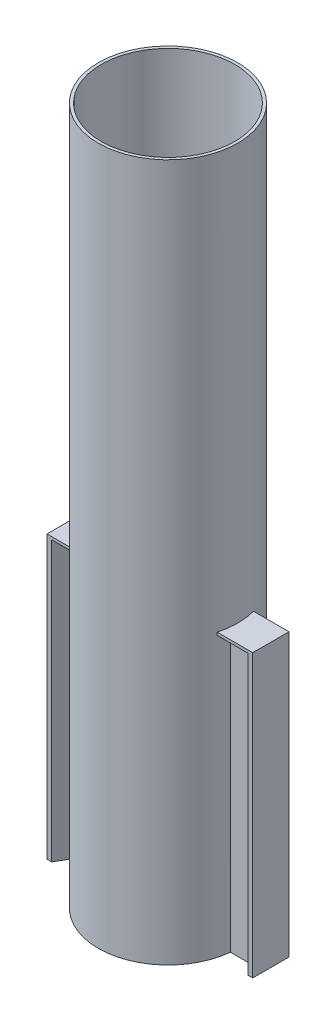
SolidWorks part; units mm, degrees
ref_plane "Спереди" through (0, 0, 0) normal (0, 0, 1) x (1, 0, 0)
ref_plane "Сверху" through (0, 0, 0) normal (0, 1, 0) x (1, 0, 0)
ref_plane "Справа" through (0, 0, 0) normal (1, 0, 0) x (0, 0, -1)
sketch "Эскиз1" plane through (0, 0, 0) normal (0, 1, 0) x (1, 0, 0)
  circle A0 centre (0, 0) radius 25
  circle A1 centre (0, 0) radius 22.5
  dimension "D1" = 50
  dimension "D2" = 45
extrude "Бобышка-Вытянуть1" add sketch "Эскиз1" along normal blind 160
sketch "Эскиз2" plane through (0, 0, 0) normal (0, -1, 0) x (1, 0, 0)
  circle A0 centre (0, 0) radius 24
  dimension "D1" = 48
extrude "Вырез-Вытянуть1" cut sketch "Эскиз2" against normal blind 22
sketch "Эскиз4" plane through (0, 160, 0) normal (0, 1, 0) x (1, 0, 0)
  circle A0 centre (0, 0) radius 25
  circle A1 centre (0, 0) radius 17
  dimension "D1" = 50
  dimension "D2" = 34
extrude "Бобышка-Вытянуть2" add sketch "Эскиз4" along normal blind 10
sketch "Эскиз5" plane through (0, 170, 0) normal (0, 1, 0) x (1, 0, 0)
  circle A0 centre (0, 0) radius 25
  circle A1 centre (0, 0) radius 19.15
  dimension "D1" = 50
  dimension "D2" = 38.3
extrude "Бобышка-Вытянуть3" add sketch "Эскиз5" along normal blind 20
sketch "Эскиз7" plane through (0, 190, 0) normal (0, 1, 0) x (1, 0, 0)
  circle A0 centre (0, 0) radius 25
  circle A1 centre (0, 0) radius 24
  dimension "D1" = 50
  dimension "D2" = 48
extrude "Бобышка-Вытянуть4" add sketch "Эскиз7" along normal blind 60
sketch "Эскиз8" plane through (0, 0, 0) normal (0, -1, 0) x (1, 0, 0)
  line L0 (0, 0) -> (0, -50.1611) construction
  line L1 (0, 0) -> (-60.6002, 0) construction
  line L2 (32.8694, 2.5) -> (35.1788, 6.5)
  line L3 (32.8694, 2.5) -> (23.8694, 2.5)
  line L4 (32.8694, 2.5) -> (32.8694, -2.5)
  line L5 (32.8694, -2.5) -> (23.8694, -2.5)
  line L6 (23.8694, 2.5) -> (23.8694, -2.5)
  line L7 (32.8694, 2.5) -> (23.8694, -2.5) construction
  line L8 (32.8694, -2.5) -> (23.8694, 2.5) construction
  line L9 (35.1788, 6.5) -> (36.8788, 6.5)
  line L10 (36.8788, 6.5) -> (36.8788, -6.5)
  line L11 (32.8694, -2.5) -> (35.1788, -6.5)
  line L12 (35.1788, -6.5) -> (36.8788, -6.5)
  circle A0 centre (0, 0) radius 24 construction
  point P1 (28.3694, 0)
  point P18 (36.8788, 0)
  circle M8 centre (0, 0) radius 25
  dimension "D1" = 9
  dimension "D2" = 5
  dimension "D3" = 4
  dimension "D4" = 30
  dimension "D5" = 1.7
extrude "Бобышка-Вытянуть5" add sketch "Эскиз8" against normal blind 100 contours L11 L12 L10 L9 L2 L4 | L5 L4 L3 M8 region at (28.9138, 0, 0) region at (35.1401, 0, 0)
sketch "Эскиз9" plane through (0, 100, 0) normal (0, 1, 0) x (1, 0, 0)
  line L1 (36.8788, 6.5) -> (23.8788, 6.5)
  line L2 (36.8788, 6.5) -> (36.8788, -6.5)
  line L3 (36.8788, -6.5) -> (23.8788, -6.5)
  line L4 (23.8788, 6.5) -> (23.8788, -6.5)
  dimension "D1" = 13
  dimension "D2" = 13
extrude "Бобышка-Вытянуть6" add sketch "Эскиз9" along normal blind 1
pattern_circular "Круговой массив1" count 2 over 360 about axis through (0, 160, 0) along (0, -1, 0) of "Бобышка-Вытянуть5", "Бобышка-Вытянуть6" reverse direction yes
sketch "Эскиз10" plane through (0, 22, 0) normal (0, -1, 0) x (1, 0, 0)
  circle A0 centre (0, 0) radius 24
  circle A1 centre (0, 0) radius 23.95
  dimension "D1" = 48
  dimension "D2" = 47.9
extrude "Бобышка-Вытянуть7" add sketch "Эскиз10" along normal blind 22
sketch "Эскиз11" plane through (0, 190, 0) normal (0, 1, 0) x (1, 0, 0)
  circle A0 centre (0, 0) radius 24
  circle A1 centre (0, 0) radius 23.95
  dimension "D1" = 48
  dimension "D2" = 47.9
extrude "Бобышка-Вытянуть8" add sketch "Эскиз11" along normal blind 60
chamfer "Фаска1" distance 10 angle 45 1 edges at (0, 22, -22.5)
chamfer "Фаска2" distance 10 angle 45 1 edges at (0, 160, 17)
